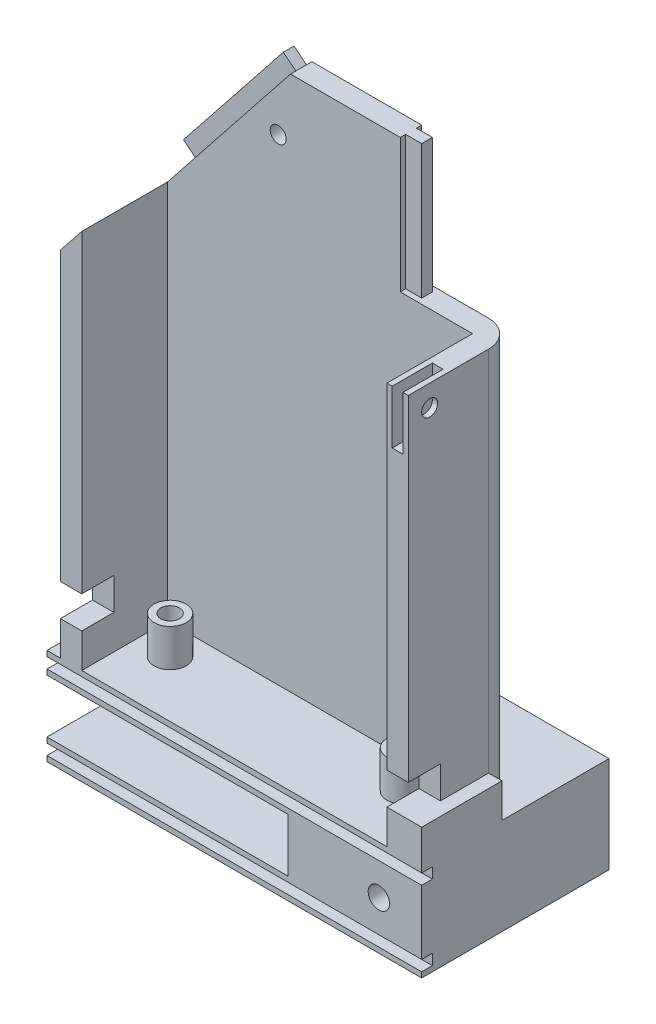
SolidWorks part; units mm, degrees
ref_plane "Front Plane" through (0, 0, 0) normal (0, 0, 1) x (1, 0, 0)
ref_plane "Top Plane" through (0, 0, 0) normal (0, 1, 0) x (1, 0, 0)
ref_plane "Right Plane" through (0, 0, 0) normal (1, 0, 0) x (0, 0, -1)
sketch "Sketch1" plane through (0, 0, 0) normal (0, 1, 0) x (1, 0, 0)
  line L1 (-32.5, -20) -> (32.5, -20)
  line L2 (-32.5, -20) -> (-32.5, 20)
  line L3 (-32.5, 20) -> (32.5, 20)
  line L4 (32.5, -20) -> (32.5, 20)
  line L5 (-32.5, -20) -> (32.5, 20) construction
  line L6 (-32.5, 20) -> (32.5, -20) construction
  point P0 (0, 0)
  dimension "D1" = 65
  dimension "D2" = 40
extrude "Boss-Extrude1" add sketch "Sketch1" along normal blind 100
shell "Shell1" thickness 4 removed face at (0, 0, 0) removed face at (0, 100, 0)
fillet "Fillet1" radius 5 4 edges at (32.5, 50, -20) (32.5, 50, 20) (-32.5, 50, -20) (-32.5, 50, 20)
sketch "Sketch2" plane through (0, 0, 0) normal (0, 0, 1) x (1, 0, 0)
  line L0 (-5.5, 100) -> (-32.5, 66)
  line L1 (28.5, 100) -> (-28.5, 100) construction
  line L2 (-32.5, 100) -> (-32.5, 0) construction
  line L3 (-32.5, 66) -> (-32.5, 100)
  line L4 (-32.5, 100) -> (-5.5, 100)
  dimension "D1" = 5.5
  dimension "D2" = 66
extrude "Cut-Extrude1" cut sketch "Sketch2" against normal through all both and the other way through all
sketch "Sketch3" plane through (0, 0, 0) normal (0, 0, 1) x (1, 0, 0)
  line L1 (32.5, 100) -> (15, 100)
  line L2 (32.5, 100) -> (32.5, 75)
  line L3 (32.5, 75) -> (15, 75)
  line L4 (15, 100) -> (15, 75)
  dimension "D1" = 25
  dimension "D2" = 17.5
extrude "Cut-Extrude2" cut sketch "Sketch3" against normal through all both and the other way through all
sketch "Sketch5" plane through (15, 0, 0) normal (1, 0, 0) x (0, 0, -1)
  line L0 (-18, 100) -> (-18, 75) construction
  line L1 (-16, 100) -> (-20, 100) construction
  line L2 (-16, 75) -> (-20, 75) construction
  line L4 (-19, 100) -> (-17, 100)
  line L5 (-19, 100) -> (-19, 75)
  line L6 (-19, 75) -> (-17, 75)
  line L7 (-17, 100) -> (-17, 75)
  dimension "D1" = 2
extrude "Boss-Extrude2" add sketch "Sketch5" along normal blind 3
mirror "Mirror1" about plane through (0, 0, 0) normal (0, 0, 1) of "Boss-Extrude2"
sketch "Sketch6" plane through (-52.0732, 41.3523, 0) normal (-0.7831, 0.6219, 0) x (0, 0, 1)
  line L0 (-18, 74.8907) -> (-18, 44.8907) construction
  line L1 (-20, 74.8907) -> (-16, 74.8907) construction
  line L3 (-19, 74.8907) -> (-17, 74.8907)
  line L4 (-19, 74.8907) -> (-19, 44.8907)
  line L5 (-19, 44.8907) -> (-17, 44.8907)
  line L6 (-17, 74.8907) -> (-17, 44.8907)
  dimension "D1" = 30
  dimension "D2" = 2
extrude "Boss-Extrude3" add sketch "Sketch6" along normal blind 3
mirror "Mirror2" about plane through (0, 0, 0) normal (0, 0, 1) of "Boss-Extrude3"
sketch "Sketch8" plane through (0, 0, 0) normal (0, 1, 0) x (1, 0, 0)
  line L1 (-35, -35) -> (35, -35)
  line L2 (-35, -35) -> (-35, 35)
  line L3 (-35, 35) -> (35, 35)
  line L4 (35, -35) -> (35, 35)
  line L5 (-35, -35) -> (35, 35) construction
  line L6 (-35, 35) -> (35, -35) construction
  point P0 (0, 0)
  dimension "D1" = 70
  dimension "D2" = 70
extrude "Boss-Extrude4" add sketch "Sketch8" against normal blind 18
sketch "Sketch10" plane through (-35, 0, 0) normal (-1, 0, 0) x (0, 0, 1)
  line L0 (-35, -9) -> (35, -9) construction
  line L1 (-30, -14) -> (30, -14)
  line L2 (-30, -14) -> (-30, -4)
  line L3 (-30, -4) -> (30, -4)
  line L4 (30, -14) -> (30, -4)
  line L5 (-30, -14) -> (30, -4) construction
  line L6 (-30, -4) -> (30, -14) construction
  line L7 (-35, -18) -> (-35, 0) construction
  line L8 (35, -18) -> (35, 0) construction
  line L9 (0, 0) -> (0, -18) construction
  line L10 (-35, -18) -> (35, -18) construction
  point P0 (0, -9)
  dimension "D1" = 60
  dimension "D2" = 10
extrude "Cut-Extrude4" cut sketch "Sketch10" against normal blind 45
sketch "Sketch23" plane through (0, 75, 0) normal (0, 1, 0) x (1, 0, 0)
  line L0 (0, 0) -> (32.5, 0) construction
  line L1 (29.5, 7.5) -> (31.5, 7.5)
  line L2 (29.5, 7.5) -> (29.5, -7.5)
  line L3 (29.5, -7.5) -> (31.5, -7.5)
  line L4 (31.5, 7.5) -> (31.5, -7.5)
  line L5 (32.5, 15) -> (32.5, -15) construction
  line L6 (28.5, 16) -> (28.5, -16) construction
  line L8 (30.5, 14.75) -> (30.5, -14.75) construction
  dimension "D1" = 2
  dimension "D2" = 15
extrude "Cut-Extrude10" cut sketch "Sketch23" against normal blind 10
sketch "Sketch27" plane through (0, 0, 0) normal (0, 1, 0) x (1, 0, 0)
  line L0 (35, -35) -> (35, 35) construction
  line L1 (-35, -35) -> (35, -35)
  line L2 (-35, -35) -> (-35, 0)
  line L3 (-35, 0) -> (35, 0)
  line L4 (35, -35) -> (35, 0)
extrude "Cut-Extrude12" cut sketch "Sketch27" against normal through all both and the other way through all
sketch "Sketch29" plane through (0, 0, 0) normal (0, 0, 1) x (1, 0, 0)
  line L0 (-35, -2) -> (35, -2) construction
  line L1 (-35, -4) -> (-35, 0) construction
  line L2 (35, -18) -> (35, 0) construction
  line L3 (-35, -1) -> (35, -1)
  line L4 (-35, -1) -> (-35, -3)
  line L5 (-35, -3) -> (35, -3)
  line L6 (35, -1) -> (35, -3)
  dimension "D1" = 2
extrude "Cut-Extrude13" cut sketch "Sketch29" against normal blind 2
sketch "Sketch30" plane through (0, 0, 0) normal (0, 0, 1) x (1, 0, 0)
  line L0 (-35, -16) -> (35, -16) construction
  line L1 (-35, -18) -> (-35, -14) construction
  line L2 (35, -18) -> (35, -3) construction
  line L4 (-35, -15) -> (35, -15)
  line L5 (-35, -15) -> (-35, -17)
  line L6 (-35, -17) -> (35, -17)
  line L7 (35, -15) -> (35, -17)
  dimension "D1" = 2
extrude "Cut-Extrude14" cut sketch "Sketch30" against normal blind 2
sketch "Sketch31" plane through (0, 0, 0) normal (0, 0, 1) x (1, 0, 0)
  line L0 (35, -15) -> (35, -3) construction
  line L1 (35, -18) -> (-35, -18) construction
  circle A0 centre (27, -9) radius 2
  dimension "D1" = 4
  dimension "D2" = 8
  dimension "D3" = 9
extrude "Cut-Extrude15" cut sketch "Sketch31" against normal through all both and the other way through all
sketch "Sketch33" plane through (0, 0, -35) normal (0, 0, -1) x (-1, 0, 0)
  circle A0 centre (-27, -9) radius 4
  dimension "D1" = 8
extrude "Cut-Extrude16" cut sketch "Sketch33" against normal blind 15
sketch "Sketch34" plane through (0, 0, 0) normal (0, 1, 0) x (1, 0, 0)
  line L1 (35, 0) -> (35, 35) construction
  line L2 (35, 35) -> (-35, 35) construction
  circle A0 centre (0, 25.5) radius 1.5
  dimension "D2" = 3
  dimension "D1" = 9.5
  dimension "D3" = 35
extrude "Cut-Extrude17" cut sketch "Sketch34" against normal through all both and the other way through all
sketch "Sketch35" plane through (0, -18, 0) normal (0, -1, 0) x (-1, 0, 0)
  circle A0 centre (0, 25.5) radius 4
  dimension "D1" = 8
extrude "Cut-Extrude18" cut sketch "Sketch35" against normal blind 3
sketch "Sketch39" plane through (0, 0, 0) normal (0, 1, 0) x (1, 0, 0)
  line L0 (-28.5, 0) -> (28.5, 0) construction
  line L2 (28.5, 16) -> (28.5, 0) construction
  circle A0 centre (21, 10.5) radius 3
  dimension "D1" = 6
  dimension "D2" = 10.5
  dimension "D3" = 7.5
extrude "Boss-Extrude7" add sketch "Sketch39" along normal blind 7
sketch "Sketch40" plane through (0, 7, 0) normal (0, 1, 0) x (1, 0, 0)
  circle A0 centre (21, 10.5) radius 1.75
  dimension "D1" = 3.5
extrude "Cut-Extrude20" cut sketch "Sketch40" against normal blind 4
pattern_linear "LPattern4" count 2 spacing 43.5 along (-1, 0, 0) of "Boss-Extrude7", "Cut-Extrude20"
sketch "Sketch41" plane through (32.5, 0, 0) normal (1, 0, 0) x (0, 0, -1)
  line L0 (0, 75) -> (0, 0) construction
  line L1 (6, 6.4) -> (0, 6.4)
  line L2 (6, 6.4) -> (6, 12.4)
  line L3 (6, 12.4) -> (0, 12.4)
  line L4 (0, 6.4) -> (0, 12.4)
  line L5 (0, 0) -> (15, 0) construction
  dimension "D1" = 6.4
  dimension "D2" = 6
  dimension "D3" = 6
extrude "Cut-Extrude21" cut sketch "Sketch41" against normal through all both and the other way through all
sketch "Sketch42" plane through (32.5, 0, 0) normal (1, 0, 0) x (0, 0, -1)
  line L1 (0, 6.4) -> (15, 6.4)
  line L2 (0, 6.4) -> (0, 0)
  line L3 (0, 0) -> (15, 0)
  line L4 (15, 6.4) -> (15, 0)
extrude "Boss-Extrude10" add sketch "Sketch42" along normal up to surface (2.5 mm away) up to face at (35, -9, -6.5)
sketch "Sketch43" plane through (32.5, 0, 0) normal (1, 0, 0) x (0, 0, -1)
  line L0 (0, 75) -> (0, 12.4) construction
  line L1 (15, 75) -> (0, 75) construction
  circle A0 centre (4, 71) radius 1.5
  dimension "D3" = 3
  dimension "D1" = 4
  dimension "D2" = 4
extrude "Cut-Extrude22" cut sketch "Sketch43" against normal blind 10 and the other way through all
sketch "Sketch45" plane through (0, 0, -35) normal (0, 0, -1) x (-1, 0, 0)
  line L0 (35, -9) -> (-35, -9) construction
  line L1 (35, -18) -> (35, 0) construction
  line L2 (-35, -18) -> (-35, 0) construction
  line L4 (29.5, -7) -> (25, -7)
  line L5 (29.5, -7) -> (29.5, -11)
  line L6 (29.5, -11) -> (25, -11)
  line L7 (25, -7) -> (25, -11)
  dimension "D1" = 5.5
  dimension "D2" = 4.5
  dimension "D3" = 4
extrude "Boss-Extrude11" add sketch "Sketch45" along normal blind 3
sketch "Sketch46" plane through (0, -7, 0) normal (0, 1, 0) x (1, 0, 0)
  line L0 (-29.5, 35) -> (-25, 38)
  line L1 (-25, 38) -> (-29.5, 38)
  line L2 (-29.5, 38) -> (-29.5, 35)
extrude "Cut-Extrude23" cut sketch "Sketch46" against normal through all
fillet "Fillet2" radius 1 1 edges at (-25, -9, -38)
sketch "Sketch49" plane through (0, 0, -20) normal (0, 0, -1) x (-1, 0, 0)
  line L0 (7.8033, 89.0595) -> (11.7188, 92.1689) construction
  line L1 (5.5, 100) -> (24.1565, 76.5067) construction
  circle A0 centre (7.8033, 89.0595) radius 1.5
  point P2 (0, 0)
  dimension "D1" = 3
  dimension "D4" = 5
  dimension "D2" = 5
  dimension "D3" = 10
extrude "Cut-Extrude24" cut sketch "Sketch49" against normal through all both and the other way through all
